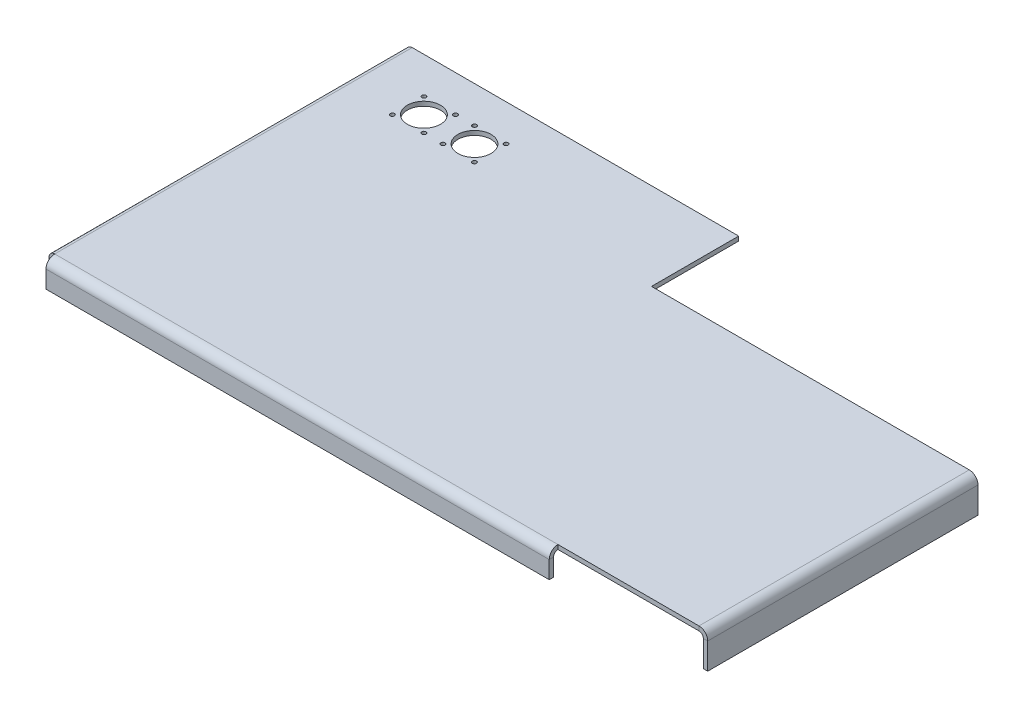
SolidWorks part; units mm, degrees
note: The reader was unsure of these and kept them because the rebuilt part matched: thickness of "Base-Flange1", "Edge-Flange1", "Edge-Flange2", "Edge-Flange3", "Sheet-Metal3", "Sheet-Metal5", "Sheet-Metal6", "Sheet-Metal7", "Sheet-Metal8", "Sheet-Metal9"; flange length of "Edge-Flange1", "Edge-Flange2", "Edge-Flange3".
material "6061-T6 (SS)"
ref_plane "X-Y Datum" through (0, 0, 0) normal (0, 0, 1) x (1, 0, 0)
ref_plane "X-Z Datum" through (0, 0, 0) normal (0, 1, 0) x (1, 0, 0)
ref_plane "Y-Z Datum" through (0, 0, 0) normal (1, 0, 0) x (0, 0, -1)
sketch "Sketch1" plane through (0, 0, 0) normal (0, 1, 0) x (1, 0, 0)
  line L1 (-232.0925, 63.7857) -> (232.0925, 63.7857)
  line L2 (-232.0925, 63.7857) -> (-232.0925, -63.7858)
  line L3 (-232.0925, -63.7858) -> (232.0925, -63.7858)
  line L4 (232.0925, 63.7857) -> (232.0925, -63.7858)
  line L5 (-232.0925, 63.7857) -> (232.0925, -63.7858) construction
  line L6 (-232.0925, -63.7858) -> (232.0925, 63.7857) construction
  point P0 (0, 0)
  dimension "D1" = 464.185
  dimension "D2" = 127.5715
sketch "Sketch2" plane through (0, 0, 0) normal (0, 1, 0) x (1, 0, 0)
  line L0 (-232.0925, 63.7857) -> (232.0925, 63.7857)
  line L1 (232.0925, 63.7857) -> (232.0925, 152.6857)
  line L2 (232.0925, 152.6857) -> (-155.8925, 152.6857)
  line L3 (-155.8925, 152.6857) -> (-232.0925, 76.4857)
  line L4 (-232.0925, 76.4857) -> (-232.0925, 63.7857)
  dimension "D1" = 45
  dimension "D2" = 12.7
  dimension "D3" = 88.9
sketch "Sketch5" plane through (0, 0, 0) normal (0, 1, 0) x (1, 0, 0)
  line L1 (-237.7745, 130.175) -> (237.7745, 130.175)
  line L2 (-237.7745, 130.175) -> (-237.7745, -130.175)
  line L3 (-237.7745, -130.175) -> (237.7745, -130.175)
  line L4 (237.7745, 130.175) -> (237.7745, -130.175)
  line L5 (-237.7745, 130.175) -> (237.7745, -130.175) construction
  line L6 (-237.7745, -130.175) -> (237.7745, 130.175) construction
  point P0 (0, 0)
  dimension "D1" = 475.549
  dimension "D2" = 260.35
base flange "Base-Flange1" sketch "Sketch5" thickness 3.175 reverse thickness direction no parameters "D1"=1
edge flange "Edge-Flange1" sketch "Sketch8" flange angle 90 flange length 19.05 flange position bend outside bend radius 3.175 thickness 3.175 relief rectangular parameters "D6"=10
sketch "Sketch8" plane through (0, -3.175, 130.175) normal (0, 0, -1) x (1, 0, 0)
  line L2 (-237.7745, 0) -> (-237.7745, 15.875)
  line L3 (-237.7745, 15.875) -> (128.7069, 15.875)
  line L9 (237.7745, 0) -> (-237.7745, 0) construction
  line L10 (128.7069, 15.875) -> (128.7069, 0)
  line L11 (128.7069, 0) -> (-237.7745, 0)
bend "EdgeBend1" bend radius 3.175 bend angle 90 parameters "D5"=1
edge flange "Edge-Flange2" sketch "Sketch11" flange angle 90 flange length 25.4 flange position material inside bend radius 3.175 thickness 3.175 relief rectangular parameters "D6"=10
sketch "Sketch11" plane through (237.7745, -3.175, 0) normal (1, 0, 0) x (0, 0, 1)
  line L2 (-130.175, 0) -> (-130.175, 22.225)
  line L3 (-130.175, 22.225) -> (130.175, 22.225)
  line L4 (130.175, 22.225) -> (130.175, 0)
  line L7 (130.175, 0) -> (-130.175, 0) construction
  line L8 (130.175, 0) -> (-130.175, 0)
bend "EdgeBend2" bend radius 3.175 bend angle 90 parameters "D5"=2
edge flange "Edge-Flange3" sketch "Sketch14" flange angle 90 flange length 25.4 flange position bend outside bend radius 1 thickness 3.175 relief rectangular parameters "D6"=10
sketch "Sketch14" plane through (-237.7745, -3.175, 0) normal (-1, 0, 0) x (0, 0, -1)
  line L2 (-130.175, 0) -> (-130.175, 22.225)
  line L3 (-130.175, 22.225) -> (130.175, 22.225)
  line L4 (130.175, 22.225) -> (130.175, 0)
  line L7 (130.175, 0) -> (-130.175, 0) construction
  line L8 (130.175, 0) -> (-130.175, 0)
bend "EdgeBend3" bend radius 1 bend angle 90 parameters "D5"=3
sketch "Sketch15" plane through (0, 0, 0) normal (0, 1, 0) x (1, 0, 0)
  line L0 (231.4245, 130.175) -> (-237.7745, 130.175) construction
  line L1 (0, 242.2169) -> (329.6475, 242.2169)
  line L2 (0, 242.2169) -> (0, 66.675)
  line L3 (0, 66.675) -> (329.6475, 66.675)
  line L4 (329.6475, 242.2169) -> (329.6475, 66.675)
  dimension "D1" = 63.5
extrude "Cut-Extrude1" cut sketch "Sketch15" against normal through all both normal cut yes
sketch "Sketch16" plane through (0, -3.175, 0) normal (0, -1, 0) x (1, 0, 0)
  line L0 (0, -130.175) -> (-237.7745, -130.175) construction
  line L1 (-203.2145, -92.075) -> (-179.0845, -92.075) construction
  line L2 (-241.9495, -130.175) -> (-241.9495, 130.175) construction
  circle A0 centre (-191.1495, -92.075) radius 12.065
  circle A1 centre (-179.6548, -80.5802) radius 1.524
  circle A2 centre (-202.6441, -80.5802) radius 1.524
  circle A3 centre (-179.6548, -103.5698) radius 1.524
  circle A4 centre (-202.6441, -103.5698) radius 1.524
  circle A5 centre (-165.8141, -80.5802) radius 1.524
  circle A6 centre (-154.3195, -92.075) radius 12.065
  circle A7 centre (-142.8248, -80.5802) radius 1.524
  circle A8 centre (-165.8141, -103.5698) radius 1.524
  circle A9 centre (-142.8248, -103.5698) radius 1.524
  point P14 (-191.1495, -92.075)
  dimension "D1" = 38.1
  dimension "D2" = 16.256
  dimension "D3" = 16.256
  dimension "D4" = 50.8
  dimension "D5" = 2
extrude "Cut-Extrude2" cut sketch "Sketch16" against normal through all both and the other way through all normal cut yes
sketch "Bend-Lines1" [suppressed] plane through (0, 0, 0) normal (0, 1, 0) x (1, 0, 0)
sketch "Bounding-Box1" [suppressed] plane through (0, 0, 0) normal (0, 1, 0) x (1, 0, 0)
sheet metal parameters "Sheet-Metal3" thickness 3.175 parameters "D1"=1
flat pattern "Flat-Pattern3" [suppressed]
sketch "Bend-Lines2" plane through (0, 0, 0) normal (0, 1, 0) x (1, 0, 0)
sketch3d "Bounding-Box2" [suppressed]
  line L0 (235.4174, -63.7858, 0) -> (-235.4174, -63.7858, 0) construction
  line L1 (235.4174, 63.7858, 0) -> (-235.4174, 63.7858, 0) construction
  line L2 (235.4174, -63.7858, 0) -> (235.4174, 63.7858, 0) construction
  line L3 (-235.4174, -63.7858, 0) -> (-235.4174, 63.7858, 0) construction
sheet metal parameters "Sheet-Metal5" thickness 3.175 parameters "D1"=1
flat pattern "Flat-Pattern3"
sketch "Bend-Lines2" plane through (0, 0, 0) normal (0, 1, 0) x (1, 0, 0)
  line L0 (-235.4174, -67.5262) -> (128.7069, -67.5262) construction
  line L1 (-235.4174, -67.5262) -> (128.7069, -67.5262) construction
sketch3d "Bounding-Box2" [suppressed]
  line L0 (235.4174, -83.9667, 0) -> (-235.4174, -83.9667, 0) construction
  line L1 (235.4174, 63.7858, 0) -> (-235.4174, 63.7858, 0) construction
  line L2 (235.4174, -83.9667, 0) -> (235.4174, 63.7858, 0) construction
  line L3 (-235.4174, -83.9667, 0) -> (-235.4174, 63.7858, 0) construction
bend of the flat pattern "Flatten-<EdgeBend1>1"
sheet metal parameters "Sheet-Metal6" thickness 3.175 parameters "D1"=1
flat pattern "Flat-Pattern3"
sketch "Bend-Lines2" plane through (0, 0, 0) normal (0, 1, 0) x (1, 0, 0)
  line L0 (-235.4174, -67.5262) -> (128.7069, -67.5262) construction
  line L1 (-235.4174, -67.5262) -> (128.7069, -67.5262) construction
  line L2 (232.8078, -63.7858) -> (232.8078, 63.7857) construction
  line L3 (232.8078, -63.7858) -> (232.8078, 63.7857) construction
sketch3d "Bounding-Box2" [suppressed]
  line L0 (255.5983, -83.9667, 0) -> (-235.4174, -83.9667, 0) construction
  line L1 (255.5983, 63.7858, 0) -> (-235.4174, 63.7858, 0) construction
  line L2 (255.5983, -83.9667, 0) -> (255.5983, 63.7858, 0) construction
  line L3 (-235.4174, -83.9667, 0) -> (-235.4174, 63.7858, 0) construction
bend of the flat pattern "Flatten-<EdgeBend1>1"
bend of the flat pattern "Flatten-<EdgeBend2>1"
sheet metal parameters "Sheet-Metal7" thickness 3.175 parameters "D1"=1
flat pattern "Flat-Pattern3"
sketch "Bend-Lines2" plane through (0, 0, 0) normal (0, 1, 0) x (1, 0, 0)
  line L0 (-237.7745, -133.9155) -> (128.7069, -133.9155) construction
  line L1 (-237.7745, -133.9155) -> (128.7069, -133.9155) construction
  line L2 (235.1649, -130.175) -> (235.1649, 130.175) construction
  line L3 (235.1649, -130.175) -> (235.1649, 130.175) construction
  line L4 (-239.8067, 130.175) -> (-239.8067, -130.175) construction
  line L5 (-239.8067, 130.175) -> (-239.8067, -130.175) construction
sketch3d "Bounding-Box2" [suppressed]
  line L0 (257.9554, -150.3559, 0) -> (-263.0639, -150.3559, 0) construction
  line L1 (257.9554, 130.175, 0) -> (-263.0639, 130.175, 0) construction
  line L2 (257.9554, -150.3559, 0) -> (257.9554, 130.175, 0) construction
  line L3 (-263.0639, -150.3559, 0) -> (-263.0639, 130.175, 0) construction
bend of the flat pattern "Flatten-<EdgeBend1>1"
bend of the flat pattern "Flatten-<EdgeBend2>1"
bend of the flat pattern "Flatten-<EdgeBend3>1"
sheet metal parameters "Sheet-Metal8" thickness 3.175 parameters "D1"=1
flat pattern "Flat-Pattern3"
sketch "Bend-Lines2" plane through (0, 0, 0) normal (0, 1, 0) x (1, 0, 0)
  line L0 (-237.7745, -133.9155) -> (128.7069, -133.9155) construction
  line L1 (-237.7745, -133.9155) -> (128.7069, -133.9155) construction
  line L2 (235.1649, -130.175) -> (235.1649, 66.675) construction
  line L3 (235.1649, -130.175) -> (235.1649, 66.675) construction
  line L4 (-239.8067, 130.175) -> (-239.8067, -130.175) construction
  line L5 (-239.8067, 130.175) -> (-239.8067, -130.175) construction
sketch3d "Bounding-Box2" [suppressed]
  line L0 (257.9554, -150.3559, 0) -> (-263.0639, -150.3559, 0) construction
  line L1 (257.9554, 130.175, 0) -> (-263.0639, 130.175, 0) construction
  line L2 (257.9554, -150.3559, 0) -> (257.9554, 130.175, 0) construction
  line L3 (-263.0639, -150.3559, 0) -> (-263.0639, 130.175, 0) construction
bend of the flat pattern "Flatten-<EdgeBend1>1"
bend of the flat pattern "Flatten-<EdgeBend2>1"
bend of the flat pattern "Flatten-<EdgeBend3>1"
sheet metal parameters "Sheet-Metal9" thickness 3.175 parameters "D1"=1
flat pattern "Flat-Pattern3"
sketch "Bend-Lines2" plane through (0, 0, 0) normal (0, 1, 0) x (1, 0, 0)
  line L0 (-237.7745, -133.9155) -> (128.7069, -133.9155) construction
  line L1 (-237.7745, -133.9155) -> (128.7069, -133.9155) construction
  line L2 (235.1649, -130.175) -> (235.1649, 66.675) construction
  line L3 (235.1649, -130.175) -> (235.1649, 66.675) construction
  line L4 (-239.8067, 130.175) -> (-239.8067, -130.175) construction
  line L5 (-239.8067, 130.175) -> (-239.8067, -130.175) construction
sketch3d "Bounding-Box2" [suppressed]
  line L0 (257.9554, -150.3559, 0) -> (-263.0639, -150.3559, 0) construction
  line L1 (257.9554, 130.175, 0) -> (-263.0639, 130.175, 0) construction
  line L2 (257.9554, -150.3559, 0) -> (257.9554, 130.175, 0) construction
  line L3 (-263.0639, -150.3559, 0) -> (-263.0639, 130.175, 0) construction
bend of the flat pattern "Flatten-<EdgeBend1>1"
bend of the flat pattern "Flatten-<EdgeBend2>1"
bend of the flat pattern "Flatten-<EdgeBend3>1"
